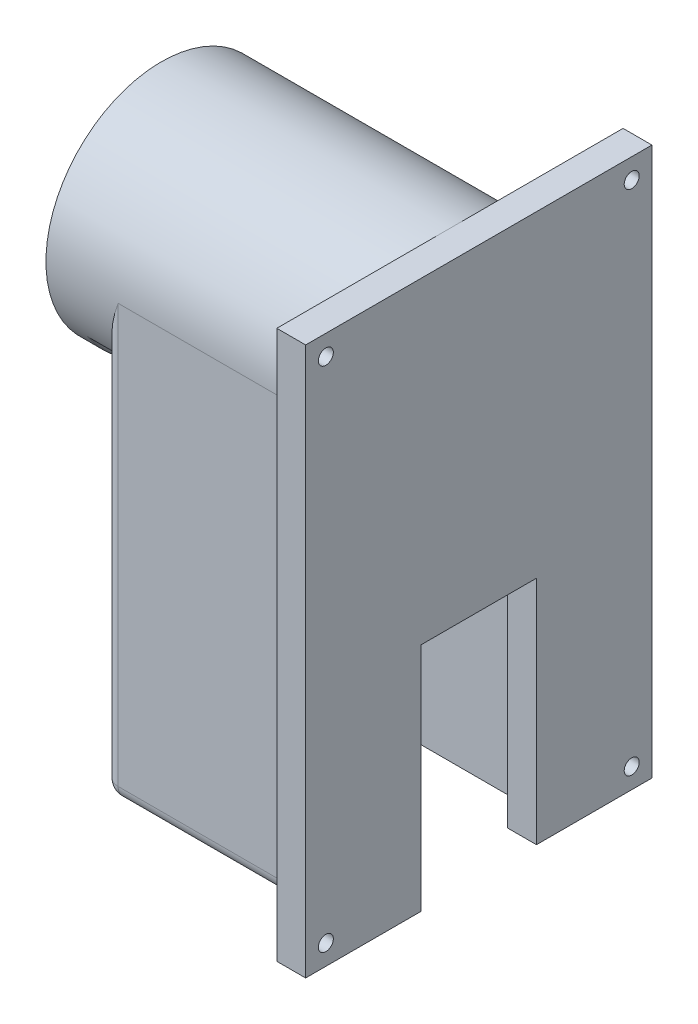
SolidWorks part; units mm, degrees
other "Markup1"
sketch "Sketch7" plane through (0, -135.1303, 40) normal (-0.0518, -0.9985, 0.0179) x (-0.029, 0.0194, 0.9994)
ref_plane "Front Plane" through (0, 0, 0) normal (0, 0, 1) x (1, 0, 0)
ref_plane "Top Plane" through (0, 0, 0) normal (0, 1, 0) x (1, 0, 0)
ref_plane "Right Plane" through (0, 0, 0) normal (1, 0, 0) x (0, 0, -1)
sketch "Sketch2" plane through (0, 0, 0) normal (1, 0, 0) x (0, 0, -1)
  circle A0 centre (0, 0) radius 40
  dimension "D1" = 80
extrude "Boss-Extrude1" add sketch "Sketch2" along normal blind 100
sketch "Sketch5" plane through (0, 0, 0) normal (-1, 0, 0) x (0, 0, 1)
  circle A0 centre (0, 0) radius 25
  dimension "D1" = 50
sketch "Sketch9" plane through (100, 0, 0) normal (1, 0, 0) x (0, 0, -1)
  line L0 (-58.1256, 0) -> (65.1542, 0) construction
  line L1 (-40, 0) -> (-40, -150)
  line L2 (-40, -150) -> (40, -150)
  line L3 (40, -150) -> (40, 0)
  line L4 (40, 0) -> (-40, 0)
  circle A0 centre (0, 0) radius 40 construction
  point P3 (-40, 0)
  point P4 (40, 0)
  dimension "D1" = 150
extrude "Boss-Extrude2" add sketch "Sketch9" against normal blind 80
extrude "Cut-Extrude2" cut sketch "Sketch5" against normal blind 50
sketch "Sketch11" plane through (20, 0, 0) normal (-1, 0, 0) x (0, 0, 1)
  line L0 (0, 0) -> (0, -234.8407) construction
  point P3 (0, -110)
  dimension "D1" = 110
sketch "Sketch13" plane through (0, -150, 0) normal (0, -1, 0) x (1, 0, 0)
  line L0 (0, 0) -> (143, 0) construction
  line L1 (100, 40) -> (100, -40) construction
  line L2 (43, 30) -> (100, 30)
  line L3 (35, 22) -> (35, -22)
  line L4 (43, -30) -> (100, -30)
  line L5 (100, 30) -> (100, -30)
  line L6 (71.5, -30) -> (71.5, 30) construction
  line L7 (35, 0) -> (100, 0) construction
  line L8 (20, 40) -> (100, 40) construction
  line L9 (20, 40) -> (20, -40) construction
  arc A0 (43, 30) -> (35, 22) centre (43, 22) ccw
  arc A1 (43, -30) -> (35, -22) centre (43, -22) cw
  point P3 (71.5, 0)
  dimension "D4" = 8
  dimension "D1" = 0
  dimension "D2" = 10
  dimension "D3" = 15
extrude "Cut-Extrude4" cut sketch "Sketch13" against normal blind 90 contours L2 A0 L3 A1 L4 L5
sketch "Sketch16" plane through (20, 0, 0) normal (-1, 0, 0) x (0, 0, 1)
  line L0 (0, 0) -> (0, -234.8407) construction
  line L1 (-30, 0) -> (30, 0)
  line L2 (-30, 0) -> (-30, -140)
  line L3 (-30, -140) -> (30, -140)
  line L4 (30, 0) -> (30, -140)
  line L5 (0, -140) -> (0, 0) construction
  line L6 (-30, -70) -> (30, -70) construction
  line L7 (40, 0) -> (40, -150) construction
  line L8 (40, -150) -> (-40, -150) construction
  arc A0 (-40, 0) -> (40, 0) centre (0, 0) ccw construction
  point P0 (0, -70)
  point P10 (0, -40)
  dimension "D1" = 10
  dimension "D2" = 10
  dimension "D3" = 0
extrude "Cut-Extrude7" cut sketch "Sketch16" against normal blind 10
sketch "Sketch17" plane through (0, -150, 0) normal (0, -1, 0) x (1, 0, 0)
  line L0 (0, 0) -> (118.8359, 0) construction
  line L1 (20, 40) -> (20, -40) construction
  line L2 (10, 30) -> (20, 30)
  line L3 (10, 30) -> (10, -30)
  line L4 (10, -30) -> (20, -30)
  line L5 (20, 30) -> (20, -30)
  line L6 (15, -30) -> (15, 30) construction
  line L7 (10, 0) -> (20, 0) construction
  line L8 (20, 40) -> (0, 40) construction
  line L9 (0, 40) -> (0, -40) construction
  point P3 (15, 0)
  dimension "D1" = 10
  dimension "D2" = 10
extrude "Cut-Extrude8" cut sketch "Sketch17" against normal blind 150
fillet "Fillet1" radius 5 1 edges at (20, -75, -40)
fillet "Fillet2" radius 5 3 edges at (20, -150, 2.5) (62.5, -150, -40) (21.4645, -150, -38.5355)
fillet "Fillet3" radius 5 3 edges at (20, -72.5, 40) (62.5, -150, 40) (21.4645, -148.5355, 40)
fillet "Fillet5" radius 5 3 edges at (20, -140, 0) (20, -83.2288, 30) (20, -83.2288, -30)
fillet "Fillet6" radius 2 3 edges at (17.5, -26.4575, 30) (10, -40, 0) (17.5, -26.4575, -30)
sketch "Sketch18" plane through (0, 0, 0) normal (-1, 0, 0) x (0, 0, 1)
  line L0 (0, 0) -> (-20.5, 0) construction
  line L1 (0, 0) -> (20.5, 0) construction
  dimension "D1" = 20.5
sketch "Sketch19" plane through (50, 0, 0) normal (-1, 0, 0) x (0, 0, 1)
  line L0 (0, 0) -> (-20.5, 0) construction
  line L1 (0, 0) -> (20.5, 0) construction
  circle A2 centre (-18, 0) radius 2.05
  circle A3 centre (18, 0) radius 2.05
  dimension "D1" = 4.1
  dimension "D2" = 4.1
  dimension "D3" = 18
  dimension "D4" = 18
extrude "Cut-Extrude10" cut sketch "Sketch19" against normal through all
sketch "Sketch20" plane through (100, 0, 0) normal (1, 0, 0) x (0, 0, -1)
  line L0 (0, 0) -> (0, -234.8407) construction
  line L1 (-60, 40) -> (60, 40)
  line L2 (-60, 40) -> (-60, -150)
  line L3 (-60, -150) -> (60, -150)
  line L4 (60, 40) -> (60, -150)
  line L5 (0, -150) -> (0, 40) construction
  line L6 (-60, -55) -> (60, -55) construction
  line L7 (-35, -150) -> (-30, -150) construction
  line L8 (-40, 0) -> (-40, -145) construction
  arc A4 (40, 0) -> (-40, 0) centre (0, 0) ccw construction
  circle A5 centre (-53, 33) radius 2.6
  circle A6 centre (-53, -143) radius 2.6
  circle A7 centre (53, -143) radius 2.6
  circle A8 centre (53, 33) radius 2.6
  point P0 (0, -55)
  point P11 (0, 40)
  dimension "D4" = 5.2
  dimension "D1" = 0
  dimension "D2" = 0
  dimension "D3" = 20
  dimension "D5" = 7
  dimension "D6" = 7
extrude "Boss-Extrude3" add sketch "Sketch20" along normal blind 10
sketch "Sketch21" plane through (0, 0, 0) normal (-1, 0, 0) x (0, 0, 1)
  line L0 (0, 0) -> (-47.8457, 0) construction
  circle A0 centre (-31.75, 0) radius 2.05
  circle A1 centre (0, 31.75) radius 2.05
  circle A2 centre (31.75, 0) radius 2.05
  circle A3 centre (0, -31.75) radius 2.05
  point P14 (0, 0)
  dimension "D2" = 4.1
  dimension "D4" = 4.1
  dimension "D1" = 31.75
  dimension "D3" = 4
extrude "Cut-Extrude11" cut sketch "Sketch21" against normal blind 10
sketch "Sketch22" plane through (30, 0, 0) normal (-1, 0, 0) x (0, 0, 1)
  line L0 (0, 0) -> (0, -171.2733) construction
  line L1 (0, -114.9) -> (0, -107.1) construction
  line L2 (-6.1, -114.9) -> (-6.1, -107.1)
  line L3 (6.1, -114.9) -> (6.1, -107.1)
  circle A0 centre (0, -111) radius 3 construction
  arc A1 (-6.1, -114.9) -> (6.1, -114.9) centre (0, -114.9) ccw
  arc A2 (6.1, -107.1) -> (-6.1, -107.1) centre (0, -107.1) ccw
  point P3 (0, -111)
  point P8 (0, -111)
  point P13 (0, -101)
  point P14 (0, -121)
  dimension "D2" = 6
  dimension "D1" = 111
  dimension "D3" = 12.2
  dimension "D4" = 10
  dimension "D5" = 10
extrude "Cut-Extrude12" cut sketch "Sketch22" against normal blind 10
sketch "Sketch23" plane through (0, -150, 0) normal (0, -1, 0) x (1, 0, 0)
  line L0 (0, 0) -> (164.7827, 0) construction
  line L1 (0, 40) -> (0, -40) construction
  line L2 (110, 60) -> (110, -60) construction
  line L3 (100, 20) -> (110, 20)
  line L4 (100, 20) -> (100, -20)
  line L5 (100, -20) -> (110, -20)
  line L6 (110, 20) -> (110, -20)
  line L7 (105, -20) -> (105, 20) construction
  line L8 (100, 0) -> (110, 0) construction
  line L9 (100, 60) -> (100, 35) construction
  point P4 (105, 0)
  dimension "D1" = 0
  dimension "D2" = 40
extrude "Cut-Extrude13" cut sketch "Sketch23" against normal blind 80
